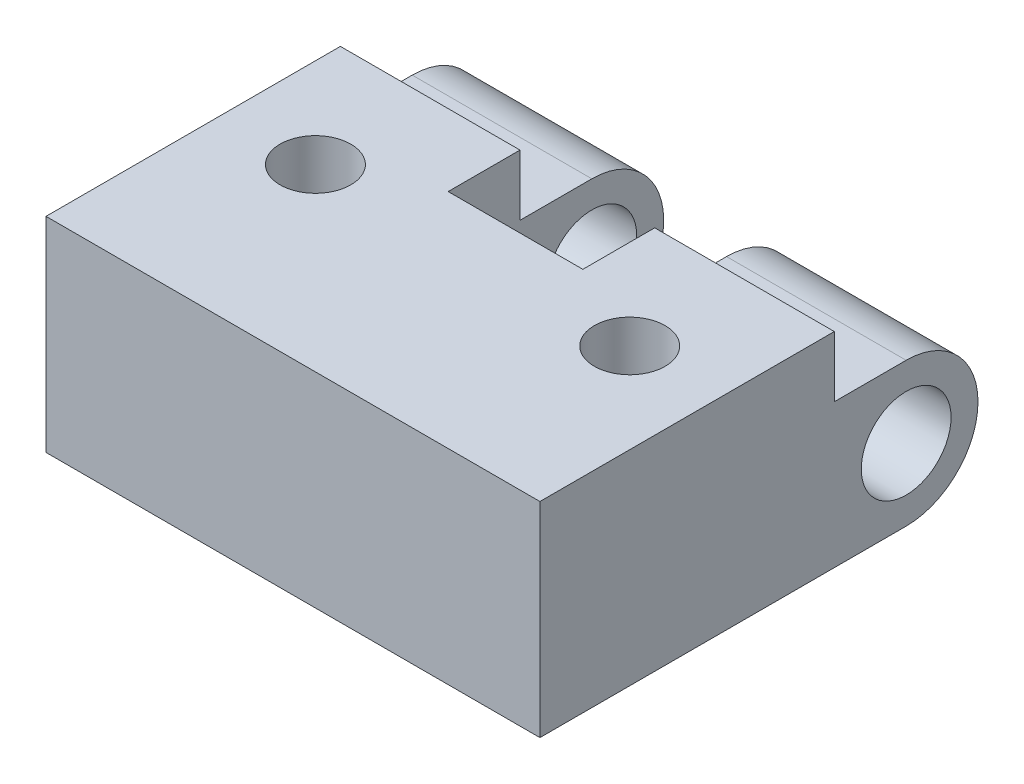
SolidWorks part; units mm, degrees
ref_plane "Front" through (0, 0, 0) normal (0, 0, 1) x (1, 0, 0)
ref_plane "Top" through (0, 0, 0) normal (0, 1, 0) x (1, 0, 0)
ref_plane "Right" through (0, 0, 0) normal (1, 0, 0) x (0, 0, -1)
sketch "Sketch2" plane through (0, 0, 0) normal (1, 0, 0) x (0, 0, -1)
  line L0 (0, 5.08) -> (0, 0)
  line L1 (0, 0) -> (13.1956, 0)
  line L2 (0, 0) -> (0, 5.08)
  line L3 (0, 5.08) -> (13.1956, 5.08)
  line L4 (13.1956, 0) -> (13.1956, 5.08)
  line L5 (0, 5.08) -> (-6.35, 5.08)
  line L6 (0, 0) -> (-6.35, 0)
  line L7 (-6.35, 5.08) -> (-6.35, 0)
  circle A0 centre (6.5978, 2.54) radius 1.5875
  arc A1 (6.5978, 5.08) -> (6.5978, 0) centre (6.5978, 2.54) cw
  point P7 (6.5978, 5.08)
  point P8 (6.5978, 0)
  dimension "D1" = 5.08
  dimension "D2" = 6.35
extrude "Boss-Extrude1" add sketch "Sketch2" along normal blind 6.35 contours L5 L7 L6 L0 | A1 L3 L0 L1 A0 region at (0, 2.54, -3.8093) region at (0, 2.54, 3.175)
sketch "Sketch3" plane through (0, 5.08, 0) normal (0, 1, 0) x (1, 0, 0)
  line L0 (3.175, -6.35) -> (3.175, 0)
  line L1 (6.35, -6.35) -> (0, -6.35) construction
  circle A0 centre (3.175, 0) radius 1.5
  dimension "D1" = 6.35
extrude "Cut-Extrude1" cut sketch "Sketch3" against normal blind 10 contours A0 region at (4.2057, 5.08, 1.0307)
sketch "Sketch4" plane through (6.35, 0, 0) normal (1, 0, 0) x (0, 0, -1)
  line L0 (6.5978, 2.54) -> (2.6291, 2.54)
  line L1 (6.5978, 2.54) -> (1.5178, 2.54)
  line L2 (6.5978, 0) -> (-6.35, 0) construction
  line L3 (1.5178, 0) -> (-6.35, 0)
  line L4 (1.5178, 0) -> (1.5178, 5.08)
  line L5 (1.5178, 5.08) -> (-6.35, 5.08)
  line L6 (-6.35, 0) -> (-6.35, 5.08)
  line M2 (6.5978, 5.08) -> (-6.35, 5.08)
  line M3 (-6.35, 5.08) -> (-6.35, 0)
  line M4 (-6.35, 0) -> (6.5978, 0)
  dimension "D1" = 3.9688
  dimension "D2" = 5.08
extrude "Boss-Extrude2" add sketch "Sketch4" along normal blind 4.7625 contours L4 M4 M2 M3 region at (6.35, 2.54, 2.4161)
ref_plane "Plane1" through (8.7313, 0, 0) normal (1, 0, 0) x (0, 0, -1)
mirror "Mirror1" about plane through (8.7313, 0, 0) normal (1, 0, 0) of "Cut-Extrude1", "Boss-Extrude1"
sketch "Sketch6" plane through (0, 5.08, 0) normal (0, 1, 0) x (1, 0, 0)
  line L0 (6.35, 4.0578) -> (0, 4.0578)
  line L1 (6.35, 6.5978) -> (6.35, 1.5178) construction
  line L2 (0, 6.5978) -> (0, -6.35) construction
  line L3 (0, 4.0578) -> (0, -6.35)
  line L4 (0, -6.35) -> (17.4625, -6.35)
  line L5 (17.4625, -6.35) -> (17.4625, 4.0578)
  line L6 (17.4625, 6.5978) -> (17.4625, -6.35) construction
  line L7 (17.4625, 4.0578) -> (11.1125, 4.0578)
  line L8 (11.1125, 6.5978) -> (11.1125, 1.5178) construction
  line L9 (11.1125, 4.0578) -> (11.1125, 1.5178)
  line L10 (11.1125, 1.5178) -> (6.35, 1.5178)
  line L11 (6.35, 1.5178) -> (6.35, 4.0578)
extrude "Boss-Extrude3" add sketch "Sketch6" along normal blind 2.15
sketch "Sketch7" plane through (0, 5.08, 0) normal (0, -1, 0) x (1, 0, 0)
  circle A0 centre (14.2875, 0) radius 1.25
  circle A1 centre (3.175, 0) radius 1.25
extrude "Cut-Extrude2" cut sketch "Sketch7" against normal through all
